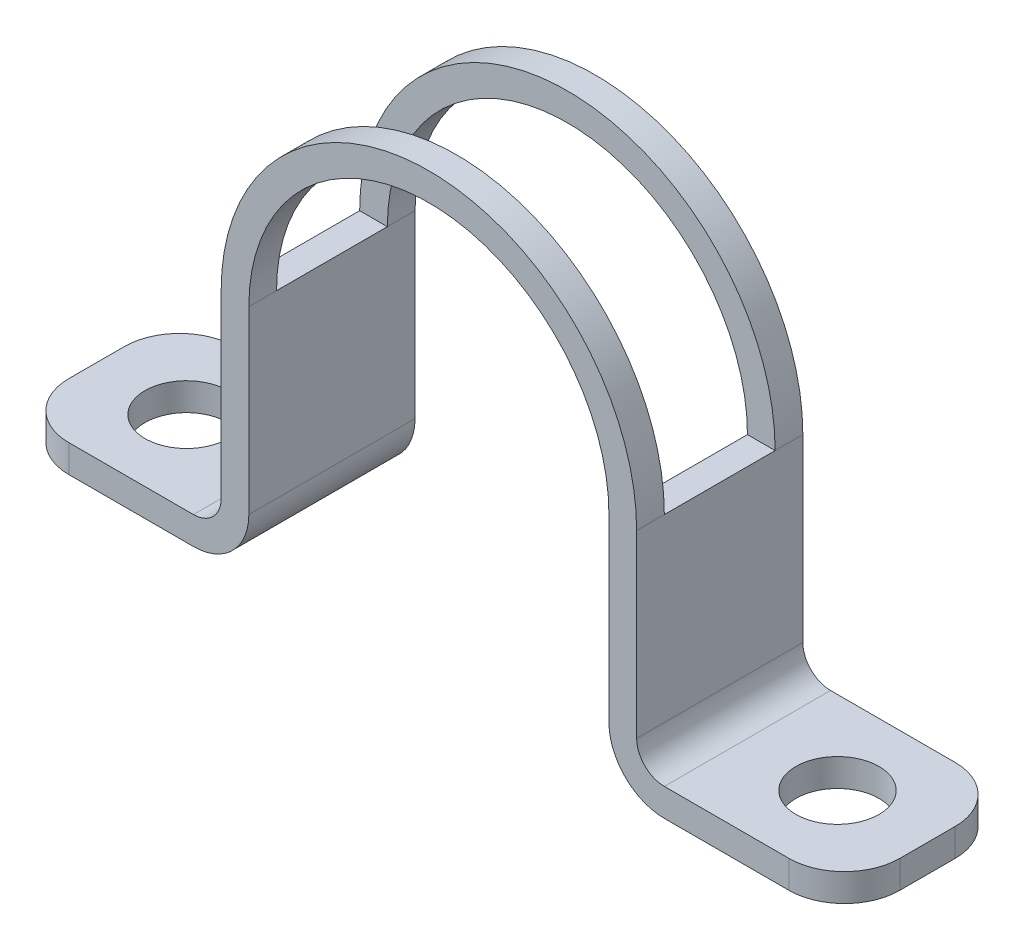
SolidWorks part; units mm, degrees
ref_plane "Front Plane" through (0, 0, 0) normal (0, 0, 1) x (1, 0, 0)
ref_plane "Top Plane" through (0, 0, 0) normal (0, 1, 0) x (1, 0, 0)
ref_plane "Right Plane" through (0, 0, 0) normal (1, 0, 0) x (0, 0, -1)
sketch "Sketch1" plane through (0, 0, 0) normal (0, 0, 1) x (1, 0, 0)
  line L0 (0, 9.6654) -> (0, -9.6654) construction
  line L1 (-15.5052, 0) -> (15.5052, 0) construction
  line L2 (-6.5, 0) -> (-6.5, -6.5)
  line L3 (-8.5, -8.5) -> (-15, -8.5)
  line L4 (-7.5, 0) -> (-7.5, -6.5)
  line L5 (-8.5, -7.5) -> (-15, -7.5)
  line L6 (-15, -7.5) -> (-15, -8.5)
  line L7 (15, -7.5) -> (15, -8.5)
  line L8 (8.5, -7.5) -> (15, -7.5)
  line L9 (7.5, 0) -> (7.5, -6.5)
  line L10 (8.5, -8.5) -> (15, -8.5)
  line L11 (6.5, 0) -> (6.5, -6.5)
  line L12 (-7.5, -6.5) -> (-6.5, -6.5)
  line L13 (6.5, -6.5) -> (7.5, -6.5)
  arc A0 (6.5, 0) -> (-6.5, 0) centre (0, 0) ccw
  arc A1 (7.5, 0) -> (-7.5, 0) centre (0, 0) ccw
  arc A2 (-6.5, -6.5) -> (-8.5, -8.5) centre (-8.5, -6.5) cw
  arc A3 (7.5, 0) -> (-7.5, 0) centre (0, 0) ccw
  arc A4 (-7.5, -6.5) -> (-8.5, -7.5) centre (-8.5, -6.5) cw
  arc A5 (7.5, -6.5) -> (8.5, -7.5) centre (8.5, -6.5) ccw
  arc A6 (6.5, -6.5) -> (8.5, -8.5) centre (8.5, -6.5) ccw
  dimension "D1" = 6.5
  dimension "D3" = 2
  dimension "D4" = 8.5
  dimension "D5" = 8.5
  dimension "D2" = 1
  dimension "D6" = 1
extrude "Boss-Extrude2" add sketch "Sketch1" along normal blind 1 contours L9 A1 L4 L12 L2 A0 L11 L13 region at (-6.7052, -3.25, 0)
extrude "Boss-Extrude3" add sketch "Sketch1<4>" along normal blind 6 contours L12 A4 L5 L6 L3 A2 | L13 A6 L10 L7 L8 A5 region at (-10.6219, -7.8644, 0) region at (10.6219, -7.8644, 0)
sketch "Sketch1<4>" plane through (0, 0, 0) normal (0, 0, 1) x (1, 0, 0) same geometry as "Sketch1"
ref_plane "Plane1" through (0, 0, 3) normal (0, 0, 1) x (1, 0, 0)
mirror "Mirror1" about plane through (0, 0, 3) normal (0, 0, 1) of "Boss-Extrude2"
sketch "Sketch3" plane through (0, -7.5, 0) normal (0, 1, 0) x (1, 0, 0)
  line L0 (-8.5, 0) -> (-15, 0) construction
  line L1 (-15, -6) -> (-15, 0) construction
  circle A0 centre (-11.75, -3) radius 1.5
  point P5 (-11.75, 0)
  point P8 (-15, -3)
  dimension "D1" = 3
extrude "Cut-Extrude1" cut sketch "Sketch3" against normal blind 6
ref_plane "Plane2" through (0, 0, 0) normal (-1, 0, 0) x (0, 0, 1)
mirror "Mirror2" about plane through (0, 0, 0) normal (-1, 0, 0) of "Cut-Extrude1"
fillet "Fillet1" radius 2 4 edges at (15, -8, 0) (15, -8, 6) (-15, -8, 6) (-15, -8, 0)
sketch "Sketch4" plane through (0, -6.5, 0) normal (0, 1, 0) x (1, 0, 0)
  line L4 (6.5, -5) -> (7.5, -5)
  line L5 (7.5, -5) -> (7.5, -1)
  line L6 (7.5, -1) -> (6.5, -1)
  line L7 (6.5, -1) -> (6.5, -5)
  line L8 (6.5, -5) -> (7.5, -5)
  line L9 (7.5, -5) -> (7.5, -1)
  line L10 (7.5, -1) -> (6.5, -1)
  line L11 (6.5, -1) -> (6.5, -5)
  line L12 (-7.5, -5) -> (-6.5, -5)
  line L13 (-6.5, -5) -> (-6.5, -1)
  line L14 (-6.5, -1) -> (-7.5, -1)
  line L15 (-7.5, -1) -> (-7.5, -5)
  line L16 (-7.5, -5) -> (-6.5, -5)
  line L17 (-6.5, -5) -> (-6.5, -1)
  line L18 (-6.5, -1) -> (-7.5, -1)
  line L19 (-7.5, -1) -> (-7.5, -5)
  dimension "D1" = 0
  dimension "D2" = 0
extrude "Boss-Extrude4" add sketch "Sketch4" along normal up to vertex (6.5 mm away) up to point (7.5, 0, 5)
